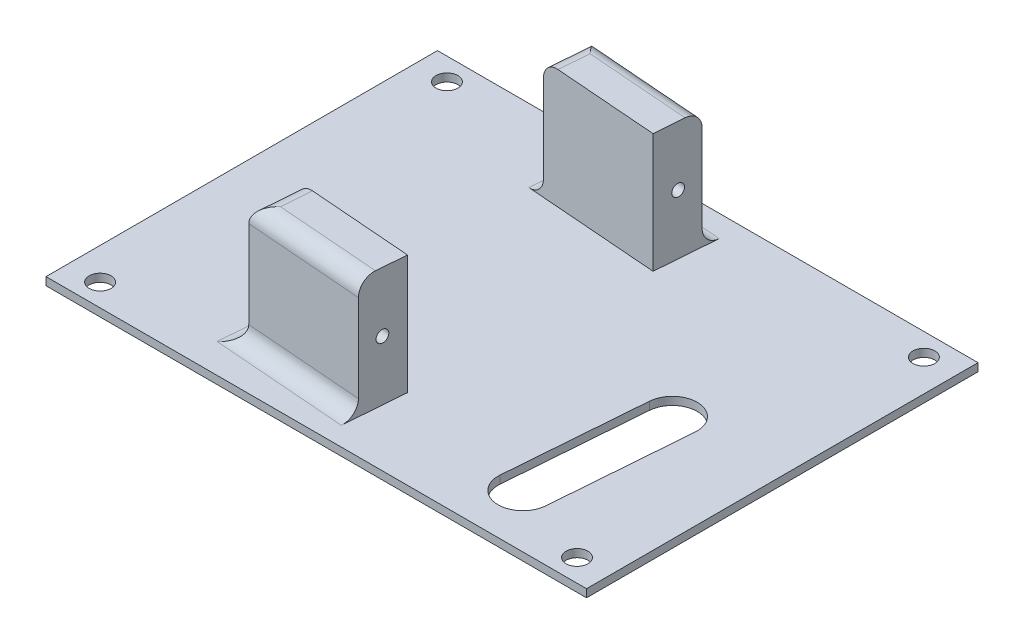
SolidWorks part; units mm, degrees
ref_plane "Ön Düzlem" through (0, 0, 0) normal (0, 0, 1) x (1, 0, 0)
ref_plane "Üst Düzlem" through (0, 0, 0) normal (0, 1, 0) x (1, 0, 0)
ref_plane "Sağ Düzlem" through (0, 0, 0) normal (1, 0, 0) x (0, 0, -1)
sketch "Çizim1" plane through (0, 0, 0) normal (0, 1, 0) x (1, 0, 0)
  line L1 (0, 0) -> (54.4, 0)
  line L2 (0, 0) -> (0, 39.4)
  line L3 (0, 39.4) -> (54.4, 39.4)
  line L4 (54.4, 0) -> (54.4, 39.4)
  dimension "D1" = 54.4
  dimension "D2" = 39.4
extrude "Yükseklik-Ekstrüzyon1" add sketch "Çizim1" along normal blind 0.8
sketch "Çizim2" plane through (0, 0.8, 0) normal (0, 1, 0) x (1, 0, 0)
  line L0 (3.2, 2.245) -> (51.2, 37.155) construction
  line L1 (3.2, 37.155) -> (51.2, 2.245) construction
  line L2 (27.2, 39.4) -> (27.2, 0) construction
  line L3 (54.4, 39.4) -> (0, 39.4) construction
  line L4 (0, 0) -> (54.4, 0) construction
  circle A4 centre (3.2, 37.155) radius 1.1
  circle A5 centre (51.2, 37.155) radius 1.1
  circle A6 centre (3.2, 2.245) radius 1.1
  circle A7 centre (51.2, 2.245) radius 1.1
  point P10 (27.2, 19.7)
  dimension "D1" = 48
  dimension "D3" = 2.2
  dimension "D2" = 34.91
extrude "Kes-Ekstrüzyon1" cut sketch "Çizim2" against normal through all
sketch "Çizim3" plane through (0, 0.8, 0) normal (0, 1, 0) x (1, 0, 0)
  line L0 (0, 0) -> (54.4, 39.4) construction
  line L1 (42.4041, 2.371) -> (44.8969, 34.4743) construction
  line L2 (42.4041, 2.371) -> (9.5031, 4.9257) construction
  line L3 (44.8969, 34.4743) -> (11.9959, 37.029) construction
  line L4 (9.5031, 4.9257) -> (11.9959, 37.029) construction
  line L5 (54.4, 39.4) -> (0, 39.4) construction
  line L6 (10.7495, 20.9773) -> (43.6505, 18.4227) construction
  line L8 (9.5031, 4.9257) -> (9.8592, 9.5119)
  line L9 (9.5031, 4.9257) -> (27.9476, 3.4935)
  line L10 (9.8592, 9.5119) -> (28.3037, 8.0797)
  line L11 (27.9476, 3.4935) -> (28.3037, 8.0797)
  line L12 (11.9959, 37.029) -> (11.6398, 32.4428)
  line L13 (11.9959, 37.029) -> (30.4404, 35.5969)
  line L14 (11.6398, 32.4428) -> (30.0843, 31.0107)
  line L15 (30.4404, 35.5969) -> (30.0843, 31.0107)
  line L16 (18.4764, 36.5258) -> (18.1203, 31.9396)
  line L17 (16.3397, 9.0087) -> (15.9836, 4.4225)
  line L18 (43.7202, 19.32) -> (42.6363, 5.362) construction
  line L19 (46.2127, 19.1264) -> (45.1288, 5.1684)
  line L20 (41.2277, 19.5135) -> (40.1438, 5.5555)
  arc A0 (46.2127, 19.1264) -> (41.2277, 19.5135) centre (43.7202, 19.32) ccw
  arc A1 (40.1438, 5.5555) -> (45.1288, 5.1684) centre (42.6363, 5.362) ccw
  point P4 (27.2, 19.7)
  point P25 (43.1783, 12.341)
  dimension "D1" = 4.44
  dimension "D2" = 30.5
  dimension "D3" = 32.2
  dimension "D4" = 23
  dimension "D5" = 18.5
  dimension "D6" = 12
  dimension "D7" = 5
  dimension "D8" = 14
  dimension "D9" = 5.4
extrude "Yükseklik-Ekstrüzyon2" add sketch "Çizim3" along normal blind 12 contours L10 L17 L9 L11 | L13 L16 L14 L15 region at (22.1437, 0.8, -6.2511) region at (24.2803, 0.8, -33.7682)
extrude "Kes-Ekstrüzyon2" cut sketch "Çizim3<3>" against normal through all contours L20 A1 L19 A0 region at (43.1783, 0.8, -12.341)
sketch "Çizim3<3>" plane through (0, 0.8, 0) normal (0, 1, 0) x (1, 0, 0) same geometry as "Çizim3"
sketch "Çizim4" plane through (27.5105, 0, 2.1361) normal (0.997, 0, 0.0774) x (0.0774, 0, -0.997)
  line L0 (5.6466, 6.8) -> (37.8466, 6.8) construction
  line L1 (5.6466, 12.8) -> (5.6466, 0.8) construction
  line L2 (37.8466, 12.8) -> (37.8466, 0.8) construction
  line L3 (21.7466, 0.8) -> (21.7466, 6.8) construction
  circle A0 centre (7.8966, 6.8) radius 0.6
  circle A1 centre (35.5966, 6.8) radius 0.6
  dimension "D1" = 27.7
  dimension "D2" = 1.2
extrude "Kes-Ekstrüzyon3" cut sketch "Çizim4" against normal blind 6
fillet "Radyus1" radius 1.6 8 edges at (16.1617, 12.8, -6.7156) (21.9656, 12.8, -3.958) (24.4584, 12.8, -36.0613) (18.2983, 12.8, -34.2327) (24.4584, 0.8, -36.0613) (18.2983, 0.8, -34.2327) (16.1617, 0.8, -6.7156) (21.9656, 0.8, -3.958)
